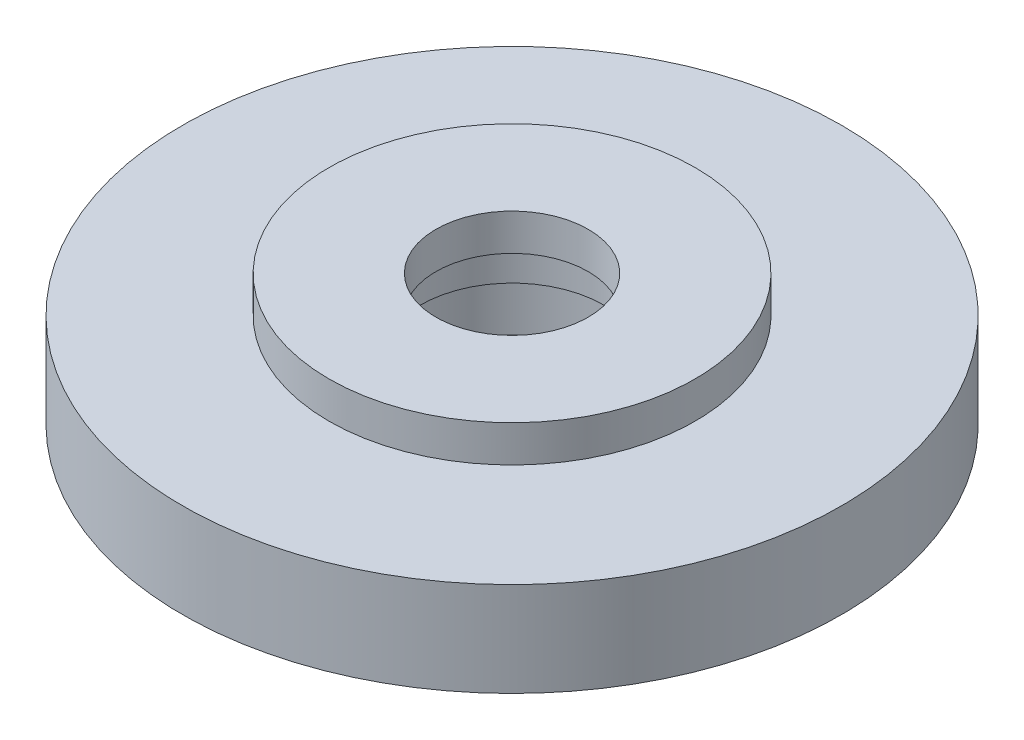
SolidWorks part; units mm, degrees
material "6061-T6 (SS)"
ref_plane "Front Plane" through (0, 0, 0) normal (0, 0, 1) x (1, 0, 0)
ref_plane "Top Plane" through (0, 0, 0) normal (0, 1, 0) x (1, 0, 0)
ref_plane "Right Plane" through (0, 0, 0) normal (1, 0, 0) x (0, 0, -1)
sketch "Sketch1" plane through (0, 0, 0) normal (0, 0, 1) x (1, 0, 0)
  line L0 (0, 0) -> (0, 11.35) construction
  line L3 (-15.875, 11.35) -> (-6.604, 11.35)
  line L4 (-6.604, 11.35) -> (-6.604, 8.175)
  line L5 (-6.604, 8.175) -> (-7.9375, 8.175)
  line L6 (-7.9375, 8.175) -> (-7.9375, 5)
  line L7 (-15.875, 11.35) -> (-15.875, 8.175)
  line L8 (-15.875, 8.175) -> (-28.575, 8.175)
  line L9 (-28.575, 8.175) -> (-28.575, 0)
  line L10 (-7.9375, 5) -> (-9.5, 5)
  line L15 (-20.6375, 0) -> (-9.5, 0)
  line L16 (-9.5, 0) -> (-9.5, 5)
  line L17 (-28.575, 0) -> (-25.4, 0)
  line L18 (-25.4, 0) -> (-25.4, 3.1369)
  line L19 (-25.4, 3.1369) -> (-20.6375, 3.1369)
  line L20 (-20.6375, 3.1369) -> (-20.6375, 0)
  point P12 (0, 0)
  point P14 (0, 0)
  point P15 (0, 9.7079)
  point P19 (0, 0)
  dimension "D1" = 13.208
  dimension "D2" = 19
  dimension "D3" = 15.875
  dimension "D4" = 3.175
  dimension "D5" = 3.175
  dimension "D6" = 12.7
  dimension "D7" = 57.15
  dimension "D8" = 3.175
  dimension "D9" = 4.7625
  dimension "D10" = 5
  dimension "D12" = 50.8
  dimension "D13" = 3.1369
revolve "Revolve1" add sketch "Sketch1" angle 360 about L0
